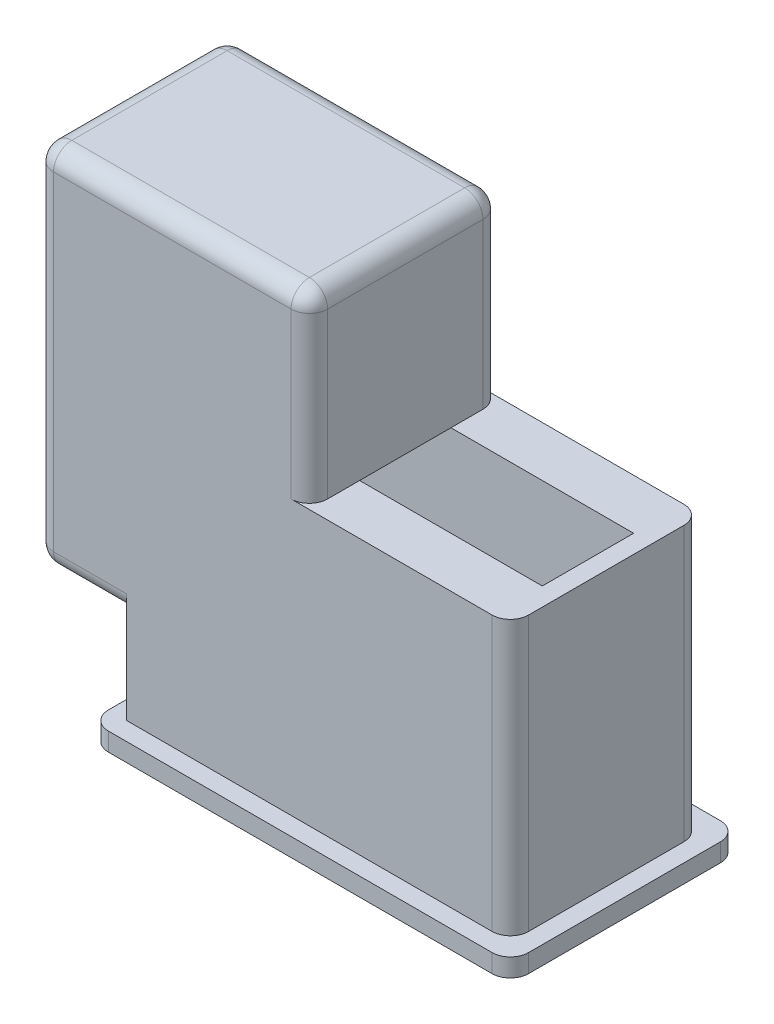
SolidWorks part; units mm, degrees
material "3003 Alloy"
ref_plane "Front Plane" through (0, 0, 0) normal (0, 0, 1) x (1, 0, 0)
ref_plane "Top Plane" through (0, 0, 0) normal (0, 1, 0) x (1, 0, 0)
ref_plane "Right Plane" through (0, 0, 0) normal (1, 0, 0) x (0, 0, -1)
sketch "Sketch2" plane through (0, 0, 0) normal (0, 1, 0) x (1, 0, 0)
  line L1 (95, -25) -> (-95, -25)
  line L2 (95, -25) -> (95, 25)
  line L3 (95, 25) -> (-95, 25)
  line L4 (-95, -25) -> (-95, 25)
  line L5 (95, -25) -> (-95, 25) construction
  line L6 (95, 25) -> (-95, -25) construction
  line L7 (105, -52.5) -> (-105, -52.5)
  line L8 (105, -52.5) -> (105, 52.5)
  line L9 (105, 52.5) -> (-105, 52.5)
  line L10 (-105, -52.5) -> (-105, 52.5)
  line L11 (105, -52.5) -> (-105, 52.5) construction
  line L12 (105, 52.5) -> (-105, -52.5) construction
  point P0 (0, 0)
  point P7 (0, 0)
  dimension "D1" = 190
  dimension "D2" = 50
  dimension "D3" = 210
  dimension "D4" = 105
extrude "Boss-Extrude2" add sketch "Sketch2" along normal blind 150
fillet "Fillet3" radius 10 1 edges at (105, 75, 52.5)
fillet "Fillet4" radius 10 1 edges at (105, 75, -52.5)
sketch "Sketch4" plane through (0, 0, 0) normal (0, 1, 0) x (1, 0, 0)
  line L1 (115, -62.5) -> (-115, -62.5)
  line L2 (115, -62.5) -> (115, 62.5)
  line L3 (115, 62.5) -> (-115, 62.5)
  line L4 (-115, -62.5) -> (-115, 62.5)
  line L5 (115, -62.5) -> (-115, 62.5) construction
  line L6 (115, 62.5) -> (-115, -62.5) construction
  point P0 (0, 0)
  dimension "D1" = 230
  dimension "D2" = 125
extrude "Boss-Extrude3" add sketch "Sketch4" against normal blind 10
fillet "Fillet5" radius 10 1 edges at (115, -5, 62.5)
fillet "Fillet6" radius 10 1 edges at (115, -5, -62.5)
fillet "Fillet7" radius 10 1 edges at (-115, -5, -62.5)
fillet "Fillet8" radius 10 1 edges at (-115, -5, 62.5)
sketch "Sketch7" plane through (0, 0, 0) normal (0, 1, 0) x (1, 0, 0)
  line L1 (-5, 25) -> (5, 25)
  line L2 (-5, 25) -> (-5, -25)
  line L3 (-5, -25) -> (5, -25)
  line L4 (5, 25) -> (5, -25)
  line L5 (-5, 25) -> (5, -25) construction
  line L6 (-5, -25) -> (5, 25) construction
  point P0 (0, 0)
  dimension "D1" = 50
  dimension "D2" = 10
extrude "Boss-Extrude4" add sketch "Sketch7" along normal blind 93.9
sketch "Sketch8" plane through (-5, 0, 0) normal (-1, 0, 0) x (0, 0, 1)
  line L0 (-25, 93.9) -> (25, 93.9) construction
  circle A0 centre (0, 93.9) radius 16.1
  dimension "D1" = 32.2
extrude "Cut-Extrude2" cut sketch "Sketch8" against normal blind 10 contours A0
sketch "Sketch10" plane through (-105, 0, 0) normal (-1, 0, 0) x (0, 0, 1)
  line L0 (-52.5, 150) -> (52.5, 150) construction
  circle A0 centre (0.0198, 93.9) radius 16.1
  point P4 (0, 150)
  dimension "D1" = 32.2
  dimension "D2" = 56.1
extrude "Cut-Extrude3" cut sketch "Sketch10" against normal blind 10 contours A0
sketch "Sketch14" plane through (0, 150, 0) normal (0, 1, 0) x (1, 0, 0)
  line L1 (-5, 52.5) -> (-5, -52.5)
  line L2 (-5, 52.5) -> (-155, 52.5)
  line L3 (-5, -52.5) -> (-155, -52.5)
  line L4 (-155, 52.5) -> (-155, -52.5)
  line L5 (95, 52.5) -> (-105, 52.5) construction
  line L6 (-105, -52.5) -> (95, -52.5) construction
  dimension "D1" = 150
extrude "Boss-Extrude6" add sketch "Sketch14" along normal blind 100
sketch "Sketch19" plane through (-155, 0, 0) normal (-1, 0, 0) x (0, 0, 1)
  line L0 (0, 250) -> (0, 150) construction
  line L1 (-52.5, 250) -> (52.5, 250) construction
  line L2 (-52.5, 150) -> (52.5, 150) construction
  line L4 (-47.5, 245) -> (47.5, 245)
  line L5 (-47.5, 245) -> (-47.5, 155)
  line L6 (-47.5, 155) -> (47.5, 155)
  line L7 (47.5, 245) -> (47.5, 155)
  line L8 (-47.5, 245) -> (47.5, 155) construction
  line L9 (-47.5, 155) -> (47.5, 245) construction
  point P6 (0, 200)
  dimension "D1" = 90
  dimension "D2" = 95
extrude "Cut-Extrude4" cut sketch "Sketch19" against normal blind 145 and the other way blind 1
sketch "Sketch22" plane through (0, 150, 0) normal (0, -1, 0) x (1, 0, 0)
  line L3 (-105, -52.5) -> (-155, -52.5)
  line L4 (-147.5, 47.5) -> (-112.5, 47.5)
  line L5 (-147.5, 47.5) -> (-147.5, -47.5)
  line L6 (-147.5, -47.5) -> (-112.5, -47.5)
  line L7 (-112.5, 47.5) -> (-112.5, -47.5)
  line L8 (-147.5, 47.5) -> (-112.5, -47.5) construction
  line L9 (-147.5, -47.5) -> (-112.5, 47.5) construction
  line L10 (-105, -52.5) -> (-105, 52.5)
  line L11 (-105, 52.5) -> (-155, 52.5)
  line L12 (-155, -52.5) -> (-155, 52.5)
  line L13 (-105, -52.5) -> (-155, 52.5) construction
  line L14 (-105, 52.5) -> (-155, -52.5) construction
  point P0 (-130, 0)
  point P6 (-130, 0)
  dimension "D1" = 35
  dimension "D2" = 95
extrude "Boss-Extrude7" add sketch "Sketch22" along normal blind 100
sketch "Sketch24" plane through (-105, 0, 0) normal (1, 0, 0) x (0, 0, -1)
  line L1 (-20.0198, 113.9) -> (19.9802, 113.9)
  line L2 (-20.0198, 113.9) -> (-20.0198, 73.9)
  line L3 (-20.0198, 73.9) -> (19.9802, 73.9)
  line L4 (19.9802, 113.9) -> (19.9802, 73.9)
  line L5 (-20.0198, 113.9) -> (19.9802, 73.9) construction
  line L6 (-20.0198, 73.9) -> (19.9802, 113.9) construction
  point P0 (-0.0198, 93.9)
  dimension "D1" = 40
  dimension "D2" = 40
extrude "Cut-Extrude5" cut sketch "Sketch24" against normal blind 10
sketch "Sketch25" plane through (-155, 0, 0) normal (-1, 0, 0) x (0, 0, 1)
  line L0 (-47.5, 245) -> (-47.5, 155)
  line L1 (-47.5, 245) -> (47.5554, 245)
  line L2 (-47.5, 155) -> (47.5554, 155)
  line L3 (47.5554, 245) -> (47.5554, 155)
extrude "Boss-Extrude9" add sketch "Sketch25" against normal blind 5
fillet "Fillet9" radius 10 4 edges at (-80, 250, -52.5) (-155, 250, 0) (-80, 250, 52.5) (-5, 250, 0)
fillet "Fillet10" radius 10 2 edges at (-155, 145, 52.5) (-152.0711, 247.0711, 49.5711)
fillet "Fillet11" radius 10 2 edges at (-155, 145, -52.5) (-152.0711, 247.0711, -49.5711)
fillet "Fillet12" radius 10 2 edges at (-5, 195, 52.5) (-7.9289, 247.0711, 49.5711)
fillet "Fillet13" radius 10 2 edges at (-5, 195, -52.5) (-7.9289, 247.0711, -49.5711)
fillet "Fillet15" radius 10 8 edges at (-125, 50, 52.5) (-130, 50, 47.5) (-147.5, 50, 0) (-130, 50, -47.5) (-155, 50, 0) (-152.0711, 50, 49.5711) (-125, 50, -52.5) (-152.0711, 50, -49.5711)
sketch "Sketch28" plane through (0, 150, 0) normal (0, -1, 0) x (1, 0, 0)
  line L0 (-130, 47.5) -> (-130, -47.5) construction
  line L1 (-112.5, 47.5) -> (-147.5, 47.5) construction
  line L2 (-147.5, -47.5) -> (-112.5, -47.5) construction
  line L4 (-147.5, 47.5) -> (-112.5, 47.5)
  line L5 (-147.5, 47.5) -> (-147.5, -47.5)
  line L6 (-147.5, -47.5) -> (-112.5, -47.5)
  line L7 (-112.5, 47.5) -> (-112.5, -47.5)
  line L8 (-147.5, 47.5) -> (-112.5, -47.5) construction
  line L9 (-147.5, -47.5) -> (-112.5, 47.5) construction
  point P6 (-130, 0)
  dimension "D1" = 35
  dimension "D2" = 95
extrude "Cut-Extrude7" cut sketch "Sketch28" against normal blind 5
